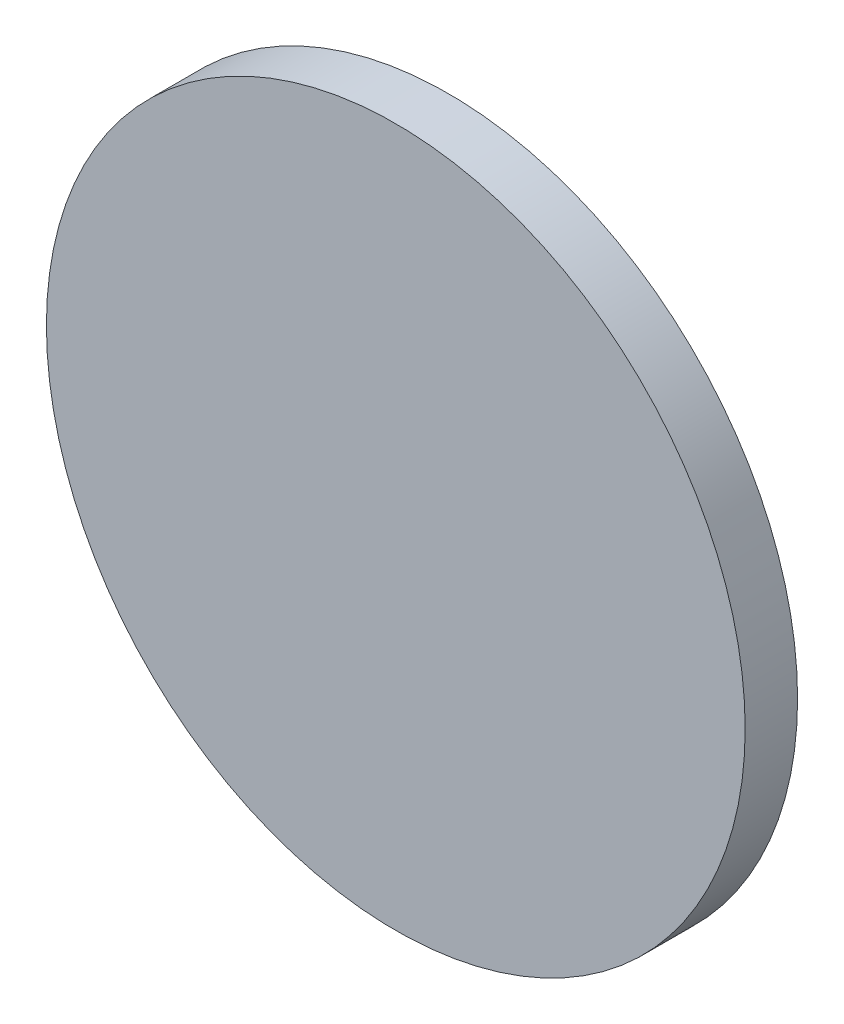
SolidWorks part; units mm, degrees
ref_plane "Plan de face" through (0, 0, 0) normal (0, 0, 1) x (1, 0, 0)
ref_plane "Plan de dessus" through (0, 0, 0) normal (0, 1, 0) x (1, 0, 0)
ref_plane "Plan de droite" through (0, 0, 0) normal (1, 0, 0) x (0, 0, -1)
sketch "Esquisse1" plane through (0, 0, 0) normal (0, 0, 1) x (1, 0, 0)
  circle A0 centre (0, 0) radius 40
extrude "Boss.-Extru.1" add sketch "Esquisse1" along normal blind 6
